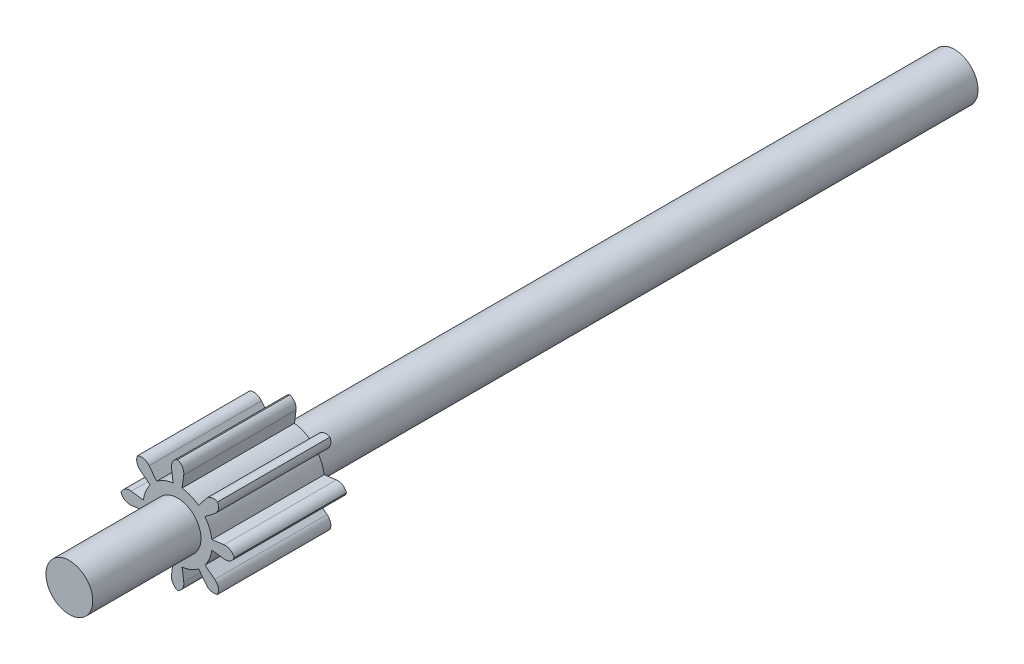
SolidWorks part; units mm, degrees
material "AISI 316 Stainless Steel Sheet (SS)"
ref_plane "Front Plane" through (0, 0, 0) normal (0, 0, 1) x (1, 0, 0)
ref_plane "Top Plane" through (0, 0, 0) normal (0, 1, 0) x (1, 0, 0)
ref_plane "Right Plane" through (0, 0, 0) normal (1, 0, 0) x (0, 0, -1)
sketch "Sketch1" plane through (0, 0, 0) normal (0, 0, 1) x (1, 0, 0)
  line L0 (0, -1.6956) -> (0, 1.7606) construction
  line L1 (-0.0966, 0.7311) -> (-0.131, 0.9914)
  line L2 (0.0966, 0.7311) -> (0.131, 0.9914)
  line L3 (0.5853, 0.4487) -> (0.7936, 0.6084)
  line L4 (0.4487, 0.5853) -> (0.6084, 0.7936)
  line L5 (0.7311, -0.0966) -> (0.9914, -0.131)
  line L6 (0.7311, 0.0966) -> (0.9914, 0.131)
  line L7 (0.4487, -0.5853) -> (0.6084, -0.7936)
  line L8 (0.5853, -0.4487) -> (0.7936, -0.6084)
  line L9 (-0.0966, -0.7311) -> (-0.131, -0.9914)
  line L10 (0.0966, -0.7311) -> (0.131, -0.9914)
  line L11 (-0.5853, -0.4487) -> (-0.7936, -0.6084)
  line L12 (-0.4487, -0.5853) -> (-0.6084, -0.7936)
  line L13 (-0.7311, 0.0966) -> (-0.9914, 0.131)
  line L14 (-0.7311, -0.0966) -> (-0.9914, -0.131)
  line L15 (-0.4487, 0.5853) -> (-0.6084, 0.7936)
  line L16 (-0.5853, 0.4487) -> (-0.7936, 0.6084)
  arc A0 (-0.5853, 0.4487) -> (-0.7311, 0.0966) centre (0, 0) ccw
  arc A1 (-0.0966, 0.7311) -> (-0.4487, 0.5853) centre (0, 0) ccw
  arc A2 (0.4487, 0.5853) -> (0.0966, 0.7311) centre (0, 0) ccw
  arc A3 (-0.131, 0.9914) -> (0, 1.21) centre (0.0722, 1.0182) cw
  arc A4 (0.131, 0.9914) -> (0, 1.21) centre (-0.0722, 1.0182) ccw
  arc A5 (0.6084, 0.7936) -> (0.8556, 0.8556) centre (0.771, 0.669) cw
  arc A6 (0.7936, 0.6084) -> (0.8556, 0.8556) centre (0.669, 0.771) ccw
  arc A7 (0.9914, 0.131) -> (1.21, 0) centre (1.0182, -0.0722) cw
  arc A8 (0.9914, -0.131) -> (1.21, 0) centre (1.0182, 0.0722) ccw
  arc A9 (0.7936, -0.6084) -> (0.8556, -0.8556) centre (0.669, -0.771) cw
  arc A10 (0.6084, -0.7936) -> (0.8556, -0.8556) centre (0.771, -0.669) ccw
  arc A11 (0.131, -0.9914) -> (0, -1.21) centre (-0.0722, -1.0182) cw
  arc A12 (-0.131, -0.9914) -> (0, -1.21) centre (0.0722, -1.0182) ccw
  arc A13 (-0.6084, -0.7936) -> (-0.8556, -0.8556) centre (-0.771, -0.669) cw
  arc A14 (-0.7936, -0.6084) -> (-0.8556, -0.8556) centre (-0.669, -0.771) ccw
  arc A15 (-0.9914, -0.131) -> (-1.21, 0) centre (-1.0182, 0.0722) cw
  arc A16 (-0.9914, 0.131) -> (-1.21, 0) centre (-1.0182, -0.0722) ccw
  arc A17 (-0.7936, 0.6084) -> (-0.8556, 0.8556) centre (-0.669, 0.771) cw
  arc A18 (-0.6084, 0.7936) -> (-0.8556, 0.8556) centre (-0.771, 0.669) ccw
  arc A19 (0.7311, 0.0966) -> (0.5853, 0.4487) centre (0, 0) ccw
  arc A20 (-0.7311, -0.0966) -> (-0.5853, -0.4487) centre (0, 0) ccw
  arc A21 (-0.4487, -0.5853) -> (-0.0966, -0.7311) centre (0, 0) ccw
  arc A22 (0.0966, -0.7311) -> (0.4487, -0.5853) centre (0, 0) ccw
  arc A23 (0.5853, -0.4487) -> (0.7311, -0.0966) centre (0, 0) ccw
  circle A24 centre (0, 0) radius 0.5
  point P65 (0, 0)
  dimension "D1" = 2.42
  dimension "D2" = 1.475
  dimension "D3" = 1
  dimension "D4" = 8
extrude "Boss-Extrude1" add sketch "Sketch1" along normal blind 2.4
extrude "Boss-Extrude3" add sketch "Sketch1<3>" along normal blind 4.7124 and the other way blind 14.2 contours A24 L0 | L0 A24 region at (-0.2122, 0, 0) region at (0.2122, 0, 0)
sketch "Sketch1<3>" plane through (0, 0, 0) normal (0, 0, 1) x (1, 0, 0) same geometry as "Sketch1"
